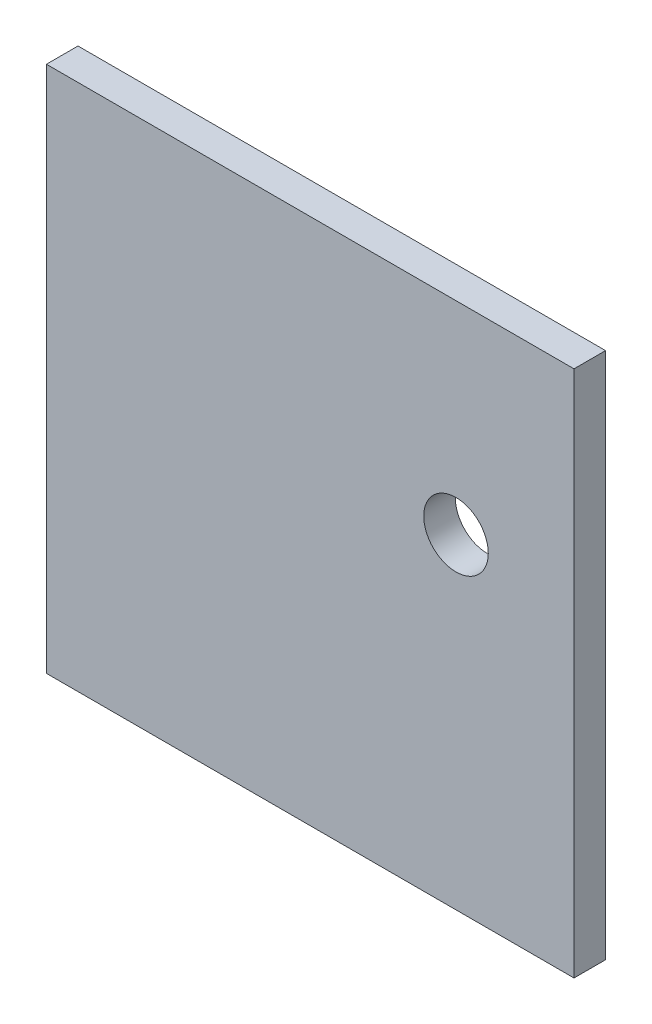
SolidWorks part; units mm, degrees
ref_plane "Front Plane" through (0, 0, 0) normal (0, 0, 1) x (1, 0, 0)
ref_plane "Top Plane" through (0, 0, 0) normal (0, 1, 0) x (1, 0, 0)
ref_plane "Right Plane" through (0, 0, 0) normal (1, 0, 0) x (0, 0, -1)
sketch "Sketch1" plane through (0, 0, 0) normal (0, 0, 1) x (1, 0, 0)
  line L4 (-76.4143, 76.4143) -> (76.4143, 76.4143)
  line L5 (76.4143, 76.4143) -> (76.4143, -76.4143)
  line L6 (76.4143, -76.4143) -> (-76.4143, -76.4143)
  line L7 (-76.4143, -76.4143) -> (-76.4143, 76.4143)
  circle A1 centre (42.2343, 17.7048) radius 9.3474
extrude "Extrude1" add sketch "Sketch1" against normal blind 9.144
sketch "Sketch5" plane through (0, 0, 0) normal (0, 0, 1) x (1, 0, 0)
  circle A0 centre (0, 0) radius 66.7479 construction
ref_axis "Axis1" through (0, 0, 0) along (0, 0, 1)
